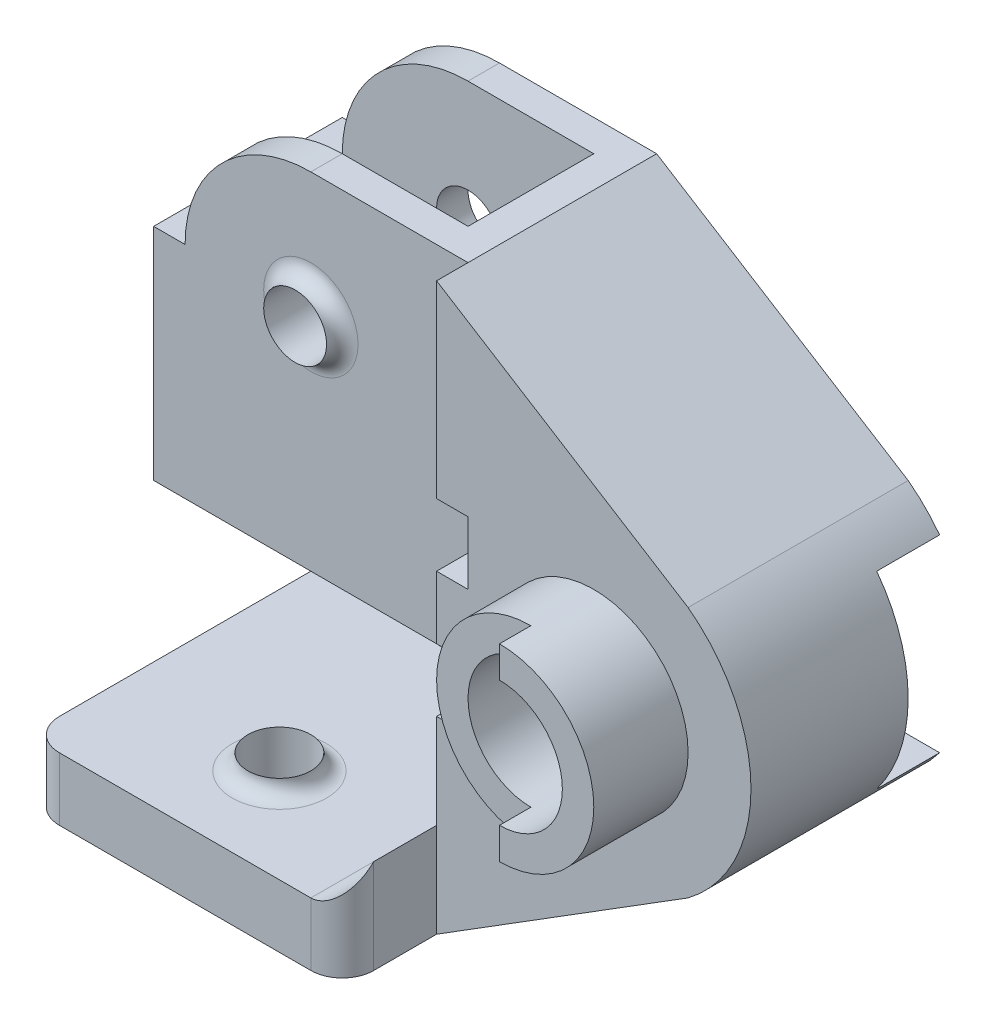
SolidWorks part; units mm, degrees
ref_plane "Front" through (0, 0, 0) normal (0, 0, 1) x (1, 0, 0)
ref_plane "Top" through (0, 0, 0) normal (0, 1, 0) x (1, 0, 0)
ref_plane "Right" through (0, 0, 0) normal (1, 0, 0) x (0, 0, -1)
sketch "Sketch1" plane through (0, 0, 0) normal (0, 0, 1) x (1, 0, 0)
  line L0 (0, 0) -> (0, 14)
  line L1 (5, 18) -> (10, 18)
  line L3 (10, 0) -> (0, 0)
  line L4 (1, 14) -> (0, 14)
  line L5 (10, 18) -> (18, 13)
  line L6 (10, 0) -> (18, 5)
  arc A0 (1, 14) -> (5, 18) centre (5, 14) cw
  circle A1 centre (5, 14) radius 1
  arc A2 (18, 13) -> (18, 5) centre (15, 9) cw
  circle A3 centre (15, 9) radius 1
  point P3 (0, 14)
  point P6 (5, 18)
  point P7 (1, 14)
  dimension "D6" = 4
  dimension "D1" = 2
  dimension "D10" = 5
  dimension "D11" = 2
  dimension "D2" = 10
  dimension "D3" = 8
  dimension "D4" = 8
  dimension "D5" = 1
  dimension "D7" = 5
  dimension "D8" = 5
  dimension "D9" = 8
extrude "Boss-Extrude1" add sketch "Sketch1" along normal blind 10
sketch "Sketch2" plane through (0, 18, 0) normal (0, 1, 0) x (1, 0, 0)
  line L1 (20, 0) -> (19, 0)
  line L2 (20, 0) -> (20, -2)
  line L3 (20, -2) -> (19, -2)
  line L4 (19, 0) -> (19, -2)
  line L5 (20, -10) -> (18, -10)
  line L6 (20, -10) -> (20, -7)
  line L7 (20, -7) -> (18, -7)
  line L8 (18, -10) -> (18, -7)
  line L9 (10, -10) -> (12, -10)
  line L10 (10, -10) -> (10, -7)
  line L11 (10, -7) -> (12, -7)
  line L12 (12, -10) -> (12, -7)
  line L13 (12, -10) -> (15, -10)
  line L14 (12, -10) -> (12, -9)
  line L15 (12, -9) -> (15, -9)
  line L16 (15, -10) -> (15, -9)
  line M14 (10, -10) -> (10, 0)
  dimension "D1" = 1
  dimension "D2" = 2
  dimension "D3" = 2
  dimension "D4" = 3
  dimension "D5" = 2
  dimension "D6" = 3
  dimension "D7" = 1
  dimension "D8" = 3
extrude "Cut-Extrude1" cut sketch "Sketch2" against normal blind 20 contours L9 L12 L11 M14 | L8 L5 L6 L7 | L1 L4 L3 L2 | L14 L15 L16 L13 region at (19.5, 18, 1) region at (19, 18, 8.5) region at (11, 18, 8.5)
sketch "Sketch3" plane through (0, 0, 10) normal (0, 0, 1) x (1, 0, 0)
  line L1 (10, 0) -> (21.3568, 0)
  line L2 (10, 0) -> (10, 18.1896)
  line L3 (10, 18.1896) -> (21.3568, 18.1896)
  line L4 (21.3568, 0) -> (21.3568, 18.1896)
  circle A0 centre (15, 9) radius 3
  dimension "D1" = 6
extrude "Cut-Extrude2" cut sketch "Sketch3" against normal blind 3
sketch "Sketch4" plane through (0, 0, 10) normal (0, 0, 1) x (1, 0, 0)
  circle A0 centre (15, 9) radius 2
  dimension "D1" = 4
extrude "Cut-Extrude3" cut sketch "Sketch4" against normal blind 4
sketch "Sketch5" plane through (0, 0, 0) normal (0, 0, -1) x (-1, 0, 0)
  line L0 (-15, 9) -> (-23.076, 9) construction
  line L1 (-15, 6) -> (-23.076, 6)
  line L2 (-15, 12) -> (-23.076, 12)
  arc A1 (-15, 6) -> (-15, 12) centre (-15, 9) ccw
  arc A2 (-23.076, 12) -> (-23.076, 6) centre (-23.076, 9) ccw
  point P3 (-19.038, 9)
  dimension "D1" = 3
extrude "Cut-Extrude4" cut sketch "Sketch5" against normal blind 2
sketch "Sketch6" plane through (0, 0, 2) normal (0, 0, -1) x (-1, 0, 0)
  circle A0 centre (-15, 9) radius 2
  dimension "D1" = 4
extrude "Cut-Extrude5" cut sketch "Sketch6" against normal blind 2
sketch "Sketch7" plane through (0, 18, 0) normal (0, 1, 0) x (1, 0, 0)
  line L0 (1, -10) -> (1, 0) construction
  line L1 (1, -1) -> (9, -1)
  line L2 (1, -1) -> (1, -5)
  line L3 (1, -5) -> (9, -5)
  line L4 (9, -1) -> (9, -5)
  line L6 (10, 0) -> (5, 0) construction
  point P6 (7.7401, -4.3812)
  point P10 (8.6951, -1)
  point P11 (10, -4.3005)
  dimension "D1" = 1
  dimension "D2" = 4
  dimension "D3" = 8
  dimension "D4" = 90
extrude "Cut-Extrude6" cut sketch "Sketch7" against normal blind 8
fillet "Fillet1" radius 1 2 edges at (1, 10, 3) (9, 10, 3)
sketch "Sketch9" plane through (0, 10, 0) normal (0, 1, 0) x (1, 0, 0)
  line L0 (9, -1) -> (5, -1) construction
  line L1 (1, -1) -> (5, -1) construction
  line L3 (1, -5) -> (1, -1) construction
  circle A0 centre (7, -3) radius 1
  circle A1 centre (3, -3) radius 1
  dimension "D4" = 2
  dimension "D5" = 2
  dimension "D1" = 2
  dimension "D2" = 2
  dimension "D3" = 4
  dimension "D6" = 2
extrude "Cut-Extrude8" cut sketch "Sketch9" against normal blind 3
sketch "Sketch10" plane through (0, 0, 10) normal (0, 0, 1) x (1, 0, 0)
  line L0 (0, 14) -> (0, 0) construction
  line L1 (0, 7) -> (9, 7)
  line L2 (0, 7) -> (0, 2)
  line L3 (0, 2) -> (9, 2)
  line L4 (10, 6) -> (10, 3)
  line L5 (10, 0) -> (10, 18) construction
  arc A0 (9, 2) -> (10, 3) centre (9, 3) ccw
  arc A1 (9, 7) -> (10, 6) centre (9, 6) cw
  point P10 (10, 2)
  dimension "D2" = 1
  dimension "D1" = 5
extrude "Cut-Extrude9" cut sketch "Sketch10" against normal blind 9
sketch "Sketch11" plane through (0, 0, 10) normal (0, 0, 1) x (1, 0, 0)
  line L0 (10, 12) -> (10, 18.5528)
  line L1 (10, 6) -> (-1.72, 6)
  line L2 (10, 8) -> (10, 10)
  line L3 (10, 18.5528) -> (-1.72, 18.5528)
  line L4 (-1.72, 6) -> (-1.72, 18.5528)
  line L5 (10, 12) -> (11, 12)
  line L7 (10, 10) -> (11, 10)
  line L8 (11, 12) -> (11, 10)
  line L9 (10, 8) -> (11, 8)
  line L11 (10, 6) -> (11, 6)
  line L12 (11, 8) -> (11, 6)
  circle M5 centre (5, 14) radius 1
  line M6 (0, 14) -> (0, 7)
  line M7 (0, 7) -> (9, 7)
  arc M8 (9, 7) -> (10, 6) centre (9, 6) cw
  line M9 (10, 6) -> (10, 18)
  line M10 (10, 18) -> (5, 18)
  arc M11 (5, 18) -> (1, 14) centre (5, 14) ccw
  line M12 (1, 14) -> (0, 14)
  dimension "D1" = 1
  dimension "D2" = 2
  dimension "D3" = 2
  dimension "D4" = 1
  dimension "D5" = 2
  dimension "D6" = 6
extrude "Cut-Extrude10" cut sketch "Sketch11" against normal blind 4 contours L8 L5 L7 M9 | L12 L9 L11 M9 | M12 M6 M7 M8 M9 M10 M11 M5 region at (5.298, 12.1411, 10) region at (10.5, 11, 10) region at (10.5, 7, 10)
sketch "Sketch12" plane through (0, 0, 1) normal (0, 0, 1) x (1, 0, 0)
  line L0 (2, 5) -> (-2.1892, 5) construction
  line L1 (2, 4) -> (-2.1892, 4)
  line L2 (2, 6) -> (-2.1892, 6)
  line L3 (0, 7) -> (9, 7) construction
  line L4 (0, 7) -> (0, 2) construction
  arc A0 (2, 4) -> (2, 6) centre (2, 5) ccw
  arc A1 (-2.1892, 6) -> (-2.1892, 4) centre (-2.1892, 5) ccw
  point P2 (-0.0946, 5)
  dimension "D2" = 1
  dimension "D1" = 2
  dimension "D3" = 2
extrude "Cut-Extrude11" cut sketch "Sketch12" against normal blind 4
sketch "Sketch13" plane through (0, 18, 0) normal (0, 1, 0) x (1, 0, 0)
  line L5 (10, -9) -> (10, -10)
  line L6 (10, -10) -> (9, -10)
  line L7 (1, -10) -> (0, -10)
  line L8 (0, -10) -> (0, -9)
  arc A0 (9, -10) -> (10, -9) centre (9, -9) ccw
  arc A1 (1, -10) -> (0, -9) centre (1, -9) cw
  point P11 (0, -10)
  dimension "D1" = 1
extrude "Cut-Extrude12" cut sketch "Sketch13" against normal blind 27
sketch "Sketch14" plane through (0, 2, 0) normal (0, 1, 0) x (1, 0, 0)
  line L0 (1, -10) -> (9, -10) construction
  line L1 (0, -1) -> (0, -9) construction
  circle A0 centre (5, -7) radius 1
  dimension "D3" = 2
  dimension "D1" = 3
  dimension "D2" = 5
extrude "Cut-Extrude13" cut sketch "Sketch14" against normal blind 27
ref_plane "Plane1" through (0, 0, 7) normal (0, 0, 1) x (1, 0, 0)
sketch "Sketch15" plane through (0, 0, 7) normal (0, 0, 1) x (1, 0, 0)
  line L0 (4, 2) -> (4, 2.5)
  line L1 (1, 2) -> (9, 2) construction
  line L2 (3.5, 2) -> (4, 2)
  line L3 (5, 0) -> (5, 1.4731) construction
  line L4 (1, 0) -> (9, 0) construction
  arc A0 (4, 2.5) -> (3.5, 2) centre (3.5, 2.5) cw
  dimension "D3" = 0.5
  dimension "D1" = 0.5
  dimension "D2" = 0.5
revolve "Revolve1" add sketch "Sketch15" angle 360 about L3
ref_plane "Plane2" through (0, 14, 0) normal (0, 1, 0) x (1, 0, 0)
sketch "Sketch16" plane through (0, 14, 0) normal (0, 1, 0) x (1, 0, 0)
  line L0 (4, -6) -> (4, -6.5)
  line L1 (4, -6) -> (3.5, -6)
  line L2 (1, -6) -> (5, -6) construction
  line L3 (5, -5) -> (5, -5.3917) construction
  arc A0 (3.5, -6) -> (4, -6.5) centre (3.5, -6.5) cw
  dimension "D1" = 0.5
  dimension "D2" = 0.5
revolve "Revolve2" add sketch "Sketch16" angle 360 about L3
